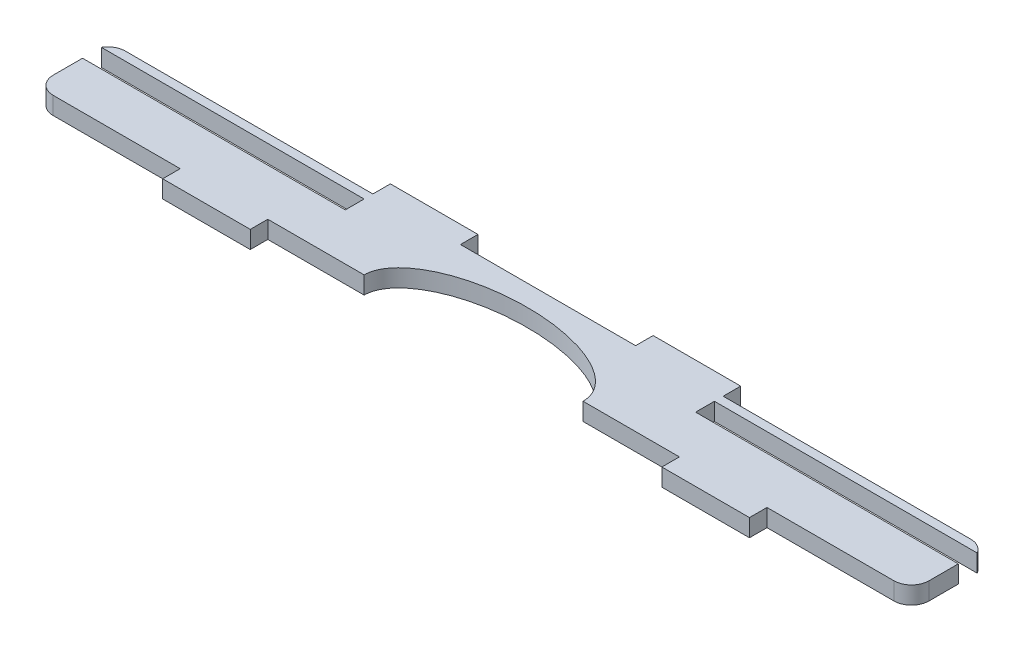
SolidWorks part; units mm, degrees
ref_plane "Front Plane" through (0, 0, 0) normal (0, 0, 1) x (1, 0, 0)
ref_plane "Top Plane" through (0, 0, 0) normal (0, 1, 0) x (1, 0, 0)
ref_plane "Right Plane" through (0, 0, 0) normal (1, 0, 0) x (0, 0, -1)
sketch "Sketch1" plane through (0, 0, 0) normal (0, 1, 0) x (1, 0, 0)
  line L1 (-127, -10.795) -> (127, -10.795)
  line L2 (-127, -10.795) -> (-127, 10.795)
  line L3 (-127, 10.795) -> (127, 10.795)
  line L4 (127, -10.795) -> (127, 10.795)
  line L5 (-127, -10.795) -> (127, 10.795) construction
  line L6 (-127, 10.795) -> (127, -10.795) construction
  point P0 (0, 0)
  dimension "D1" = 254
  dimension "D2" = 21.59
extrude "Wall-Base" add sketch "Sketch1" along normal blind 5.08
sketch "Sketch2" plane through (0, 0, -10.795) normal (0, 0, -1) x (-1, 0, 0)
  line L0 (127, 5.08) -> (50.8, 5.08) construction
  line L1 (-127, 5.08) -> (127, 5.08) construction
  line L2 (-127, 0) -> (127, 0) construction
  line L3 (50.8, 5.08) -> (25.4, 5.08)
  line L4 (50.8, 5.08) -> (50.8, 0)
  line L5 (50.8, 0) -> (25.4, 0)
  line L6 (25.4, 5.08) -> (25.4, 0)
  dimension "D1" = 76.2
  dimension "D2" = 25.4
extrude "Tab" add sketch "Sketch2" along normal blind 5.08
ref_axis "Axis1" through (-127, 5.08, 0) along (0, -1, 0)
ref_axis "Axis2" through (0, 5.08, 10.795) along (0, -1, 0)
ref_plane "Plane1" through (0, 0, 0) normal (-1, 0, 0) x (0, -1, 0)
ref_plane "Plane2" through (0, 0, 0) normal (0, 0, -1) x (0, -1, 0)
sketch "Sketch7" plane through (0, 0, 10.795) normal (0, 0, 1) x (1, 0, 0)
  line L0 (-127, 2.54) -> (-85.09, 2.54) construction
  line L1 (-127, 5.08) -> (-127, 0) construction
  line L2 (-127, 5.08) -> (127, 5.08) construction
  line L3 (-85.09, 5.08) -> (-59.69, 5.08)
  line L4 (-85.09, 5.08) -> (-85.09, 0)
  line L5 (-85.09, 0) -> (-59.69, 0)
  line L6 (-59.69, 5.08) -> (-59.69, 0)
  line L7 (-127, 0) -> (127, 0) construction
  point P12 (-102.2883, 2.54)
  dimension "D1" = 25.4
  dimension "D2" = 41.91
extrude "Boss-Extrude1" add sketch "Sketch7" along normal blind 5.08
mirror "Mirror1" about plane through (0, 0, 0) normal (-1, 0, 0) of "Tab"
sketch "Sketch3" plane through (0, 5.08, 0) normal (0, 1, 0) x (1, 0, 0)
  ellipse E0 centre (0, -10.795) end of major axis (31.75, -10.795) minor radius 15.5155
extrude "Wheel-Well-Cut" cut sketch "Sketch3" against normal through all
sketch "Sketch6" plane through (0, 5.08, 0) normal (0, 1, 0) x (1, 0, 0)
  line L0 (-127, 10.795) -> (-127, 8.255) construction
  line L2 (-127, 10.795) -> (-127, -10.795) construction
  line L8 (-127, 8.255) -> (-50.8, 8.255)
  line L9 (-127, 8.255) -> (-127, 2.794)
  line L10 (-127, 2.794) -> (-50.8, 2.794)
  line L11 (-50.8, 8.255) -> (-50.8, 2.794)
  dimension "D1" = 2.54
  dimension "D2" = 76.2
  dimension "D3" = 5.461
extrude "Cut-Extrude5" cut sketch "Sketch6" against normal through all
mirror "Mirror4" about plane through (0, 0, 0) normal (-1, 0, 0) of "Cut-Extrude5"
fillet "Fillet2" radius 5.08 4 edges at (127, 2.54, -10.795) (127, 2.54, 10.795) (-127, 2.54, -10.795) (-127, 2.54, 10.795)
mirror "Mirror5" about plane through (0, 0, 0) normal (-1, 0, 0) of "Boss-Extrude1"
equation "\"Foamcore\" = .1in"
equation "\"MDF\" = .2in"
equation "\"Gmaterial\"= \"MDF\""
equation "\"PVC-ID\" = \"1.590in\""
equation "\"PVC-OD\" = \"1.900in\""
equation "\"D1@Wall-Base\" = \"Gmaterial\""
equation "\"D1@Tab\" = \"Gmaterial\""
equation "\"D3@Sketch6\"=\"Gmaterial\"+.015"
equation "\"D1@Boss-Extrude1\"=\"Gmaterial\""
